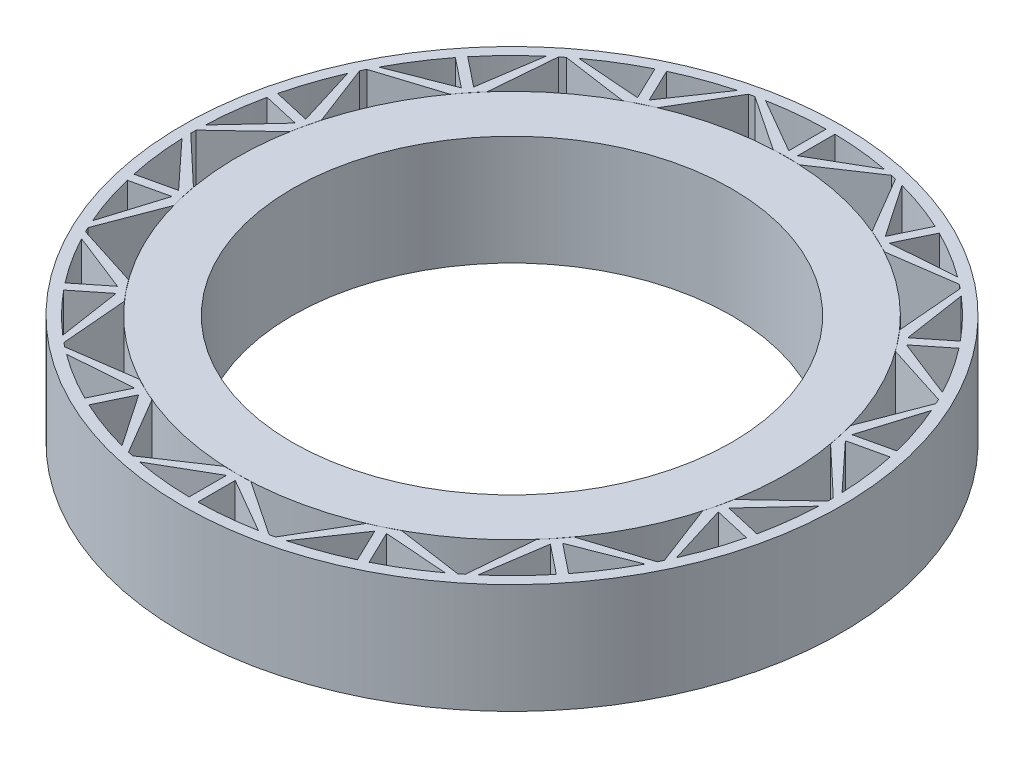
SolidWorks part; units mm, degrees
ref_plane "Спереди" through (0, 0, 0) normal (0, 0, 1) x (1, 0, 0)
ref_plane "Сверху" through (0, 0, 0) normal (0, 1, 0) x (1, 0, 0)
ref_plane "Справа" through (0, 0, 0) normal (1, 0, 0) x (0, 0, -1)
sketch "Эскиз1" plane through (0, 0, 0) normal (0, 1, 0) x (1, 0, 0)
  circle A0 centre (0, 0) radius 100
  circle A1 centre (0, 0) radius 125
  dimension "D1" = 250
  dimension "D2" = 200
extrude "Бобышка-Вытянуть1" add sketch "Эскиз1" along normal blind 50
sketch "Эскиз3" plane through (0, 0, 0) normal (0, -1, 0) x (-1, 0, 0)
  circle A0 centre (0, 0) radius 145
  circle A1 centre (0, 0) radius 150
  dimension "D1" = 300
  dimension "D2" = 290
extrude "Бобышка-Вытянуть3" add sketch "Эскиз3" against normal blind 50 separate body
sketch "Эскиз2" plane through (0, 0, 0) normal (0, -1, 0) x (1, 0, 0)
  line L0 (0, 0) -> (0, 145) construction
  line L3 (-2, 124.984) -> (-2, 144.9862)
  line L4 (2, 124.984) -> (2, 144.9862)
  circle A0 centre (0, 0) radius 125 construction
  arc A1 (-2, 124.984) -> (0, 125) centre (-0.5, 62.5) cw
  circle A2 centre (0, 0) radius 100 construction
  circle A3 centre (0, 0) radius 145 construction
  arc A4 (-2, 144.9862) -> (2, 144.9862) centre (0, 0) cw
  arc A5 (2, 124.984) -> (0, 125) centre (0.5, 62.5) ccw
  point P9 (0, 0)
  point P10 (0, 0)
  point P16 (0, 0)
  dimension "D1" = 4
extrude "Бобышка-Вытянуть2" add sketch "Эскиз2" against normal blind 50 separate body
pattern_circular "Круговой массив7" count 14 over 360 about axis through (0, 0, 0) along (0, 1, 0) of "Бобышка-Вытянуть2"
sketch "Эскиз4" plane through (0, 0, 0) normal (0, -1, 0) x (1, 0, 0)
  line L1 (-31.0603, 141.6342) -> (-6, 124.8559)
  line L2 (-2, 124.984) -> (7.953, 124.984) construction
  line L3 (-2, 124.984) -> (-2, 127.984)
  line L4 (-2, 144.9862) -> (-2, 124.984) construction
  line L5 (-2, 127.984) -> (-27.0603, 142.4526)
  line L6 (0, 148.9306) -> (0, 117.9564) construction
  line L7 (31.0603, 141.6342) -> (6, 124.8559)
  line L8 (2, 127.984) -> (27.0603, 142.4526)
  line L9 (2, 124.984) -> (2, 127.984)
  arc A0 (61.1052, 131.4958) -> (-61.1052, 131.4958) centre (0, 0) ccw construction
  arc A1 (-27.0603, 142.4526) -> (-31.0603, 141.6342) centre (0, 0) ccw
  circle A2 centre (0, 0) radius 125 construction
  arc A3 (-6, 124.8559) -> (-2, 124.984) centre (0, 0) cw
  arc A4 (6, 124.8559) -> (2, 124.984) centre (0, 0) ccw
  arc A5 (27.0603, 142.4526) -> (31.0603, 141.6342) centre (0, 0) cw
  dimension "D1" = 4
  dimension "D2" = 4
  dimension "D3" = 3
  dimension "D4" = 150
extrude "Бобышка-Вытянуть8" add sketch "Эскиз4" against normal up to surface (50 mm away) up to face at (0, 50, -10.1185)
pattern_circular "Круговой массив9" count 14 over 360 about axis through (0, 50, 0) along (0, 1, 0) of "Бобышка-Вытянуть8"
